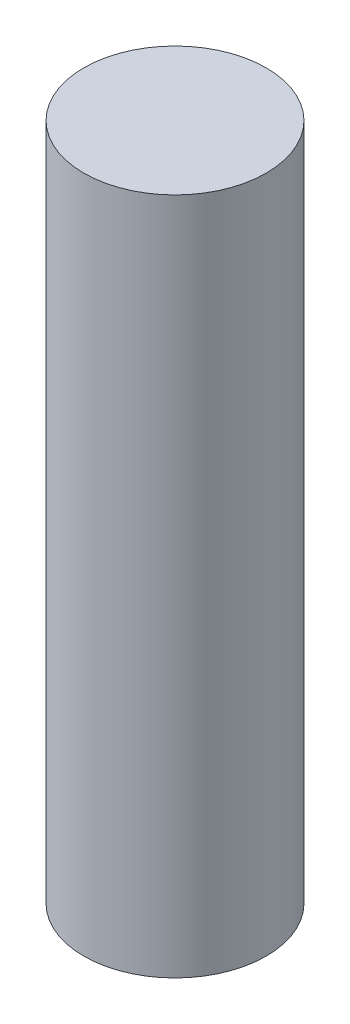
SolidWorks part; units mm, degrees
ref_plane "Front Plane" through (0, 0, 0) normal (0, 0, 1) x (1, 0, 0)
ref_plane "Top Plane" through (0, 0, 0) normal (0, 1, 0) x (1, 0, 0)
ref_plane "Right Plane" through (0, 0, 0) normal (1, 0, 0) x (0, 0, -1)
sketch "Sketch1" plane through (0, 0, 0) normal (0, 1, 0) x (1, 0, 0)
  circle A0 centre (0, 0) radius 2.475
  dimension "D1" = 4.95
extrude "Boss-Extrude1" add sketch "Sketch1" along normal blind 18.4
